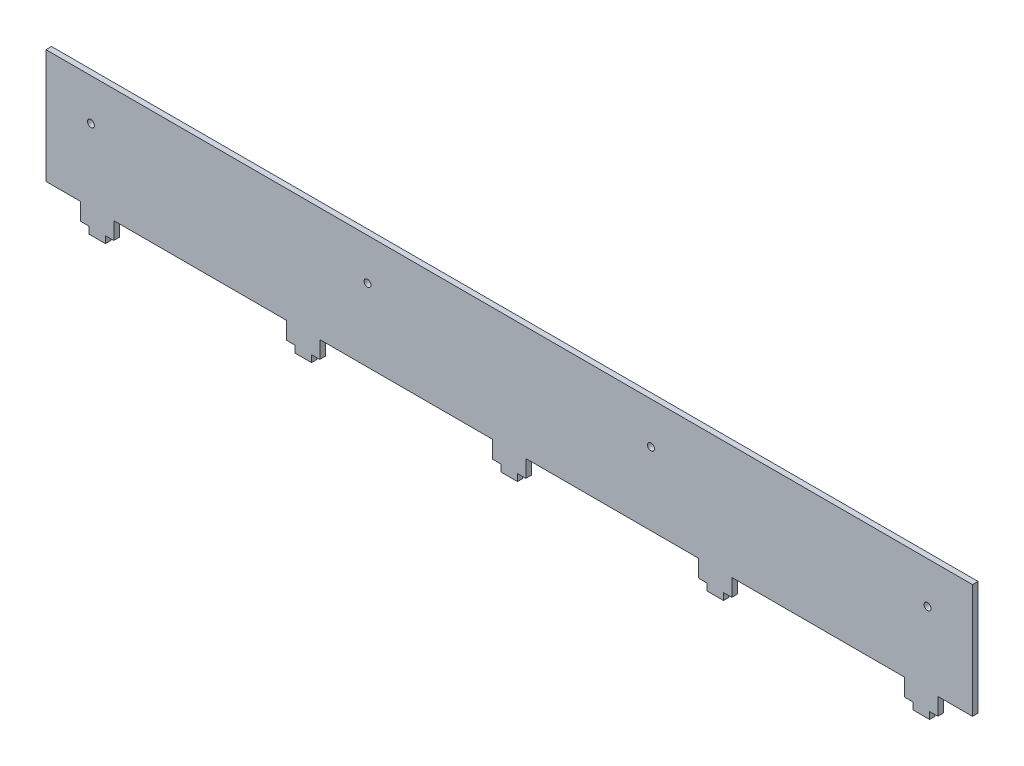
SolidWorks part; units mm, degrees
ref_plane "Спереди" through (0, 0, 0) normal (0, 0, 1) x (1, 0, 0)
ref_plane "Сверху" through (0, 0, 0) normal (0, 1, 0) x (1, 0, 0)
ref_plane "Справа" through (0, 0, 0) normal (1, 0, 0) x (0, 0, -1)
sketch "Эскиз1" plane through (0, 0, 0) normal (0, 0, 1) x (1, 0, 0)
  line L1 (-335, -47.5) -> (335, -47.5)
  line L2 (-335, -47.5) -> (-335, 47.5)
  line L3 (-335, 47.5) -> (335, 47.5)
  line L4 (335, -47.5) -> (335, 47.5)
  line L5 (0, 47.5) -> (0, -47.5) construction
  line L6 (-335, 0) -> (335, 0) construction
  point P0 (0, 0)
  dimension "D1" = 95
  dimension "D2" = 670
extrude "Бобышка-Вытянуть1" add sketch "Эскиз1" along normal mid plane 4
sketch "Эскиз2" plane through (0, 0, 2) normal (0, 0, 1) x (1, 0, 0)
  line L0 (-335, -47.5) -> (335, -47.5) construction
  line L9 (-435, -35.0456) -> (-310, -35.0456)
  line L10 (-435, -35.0456) -> (-435, -47.5)
  line L11 (-435, -47.5) -> (-310, -47.5)
  line L12 (-310, -35.0456) -> (-310, -47.5)
  line L14 (-286, -35.0456) -> (-161, -35.0456)
  line L15 (-286, -35.0456) -> (-286, -47.5)
  line L16 (-286, -47.5) -> (-161, -47.5)
  line L17 (-161, -35.0456) -> (-161, -47.5)
  line L18 (-137, -35.0456) -> (-12, -35.0456)
  line L19 (-137, -35.0456) -> (-137, -47.5)
  line L20 (-137, -47.5) -> (-12, -47.5)
  line L21 (-12, -35.0456) -> (-12, -47.5)
  line L22 (12, -35.0456) -> (137, -35.0456)
  line L23 (12, -35.0456) -> (12, -47.5)
  line L24 (12, -47.5) -> (137, -47.5)
  line L25 (137, -35.0456) -> (137, -47.5)
  line L26 (161, -35.0456) -> (286, -35.0456)
  line L27 (161, -35.0456) -> (161, -47.5)
  line L28 (161, -47.5) -> (286, -47.5)
  line L29 (286, -35.0456) -> (286, -47.5)
  line L30 (310, -35.0456) -> (435, -35.0456)
  line L31 (310, -35.0456) -> (310, -47.5)
  line L32 (310, -47.5) -> (435, -47.5)
  line L33 (435, -35.0456) -> (435, -47.5)
  point P25 (-137, -41.2728)
  point P26 (137, -41.2728)
  dimension "D6" = 125
  dimension "D3" = 125
  dimension "D4" = 125
  dimension "D9" = 125
  dimension "D11" = 125
  dimension "D5" = 24
  dimension "D2" = 24
  dimension "D7" = 24
  dimension "D8" = 24
  dimension "D10" = 24
  dimension "D12" = 125
  dimension "D13" = 12
extrude "Вырез-Вытянуть1" cut sketch "Эскиз2" against normal through all
sketch "Эскиз3" [suppressed] plane through (0, 0, 2) normal (0, 0, 1) x (1, 0, 0)
  line L0 (-328, 5.9544) -> (-328, -6.0456)
  line L1 (-328, -6.0456) -> (-318, -6.0456)
  line L2 (-318, -6.0456) -> (-318, -20.0456)
  line L3 (-318, -20.0456) -> (318, -20.0456)
  line L4 (318, -20.0456) -> (318, -6.0456)
  line L5 (318, -6.0456) -> (328, -6.0456)
  line L6 (328, -6.0456) -> (328, 5.9544)
  line L7 (328, 5.9544) -> (290, 5.9544)
  line L8 (290, 5.9544) -> (280, 35.5)
  line L9 (280, 35.5) -> (240, 35.5)
  line L10 (240, 35.5) -> (230, 5.9544)
  line L11 (230, 5.9544) -> (-230, 5.9544)
  line L12 (-230, 5.9544) -> (-240, 35.5)
  line L13 (-240, 35.5) -> (-280, 35.5)
  line L14 (-280, 35.5) -> (-290, 5.9544)
  line L15 (-290, 5.9544) -> (-328, 5.9544)
  line L16 (0, 0) -> (0, 91.1092) construction
  line L17 (-260, 35.5) -> (-260, 12.7826) construction
  line L18 (260, 35.5) -> (260, 0) construction
  line L19 (-12, -35.0456) -> (-137, -35.0456) construction
  line L20 (-335, 47.5) -> (-335, -35.0456) construction
  line L21 (335, 47.5) -> (-335, 47.5) construction
  dimension "D1" = 15
  dimension "D2" = 14
  dimension "D3" = 12
  dimension "D4" = 60
  dimension "D5" = 38
  dimension "D6" = 7
  dimension "D7" = 17
  dimension "D8" = 12
  dimension "D9" = 40
extrude "Вырез-Вытянуть2" [suppressed] cut sketch "Эскиз3" against normal through all
fillet "Скругление1" [suppressed] radius 10
fillet "Скругление6" [suppressed] radius 2
sketch "Эскиз4" [suppressed] plane through (0, 0, 2) normal (0, 0, 1) x (1, 0, 0)
  circle A1 centre (-302.5, -27.5) radius 2.5
  circle A2 centre (-302.5, -27.5) radius 2.5
  circle A3 centre (0, -27.5) radius 2.5
  circle A4 centre (0, -27.5) radius 2.5
  circle A5 centre (302.5, -27.5) radius 2.5
  circle A6 centre (302.5, -27.5) radius 2.5
  circle A7 centre (-102.5, 17.5) radius 2.5
  circle A8 centre (-102.5, 17.5) radius 2.5
  circle A9 centre (102.5, 17.5) radius 2.5
  circle A10 centre (102.5, 17.5) radius 2.5
  circle A11 centre (-302.5, 17.5) radius 2.5
  circle A12 centre (-302.5, 17.5) radius 2.5
  circle A13 centre (302.5, 17.5) radius 2.5
  circle A14 centre (302.5, 17.5) radius 2.5
  dimension "D1" = 0
  dimension "D2" = 0
  dimension "D3" = 0
  dimension "D4" = 0
  dimension "D5" = 0
  dimension "D6" = 0
  dimension "D7" = 0
extrude "Вырез-Вытянуть3" [suppressed] cut sketch "Эскиз4" against normal through all
sketch "Эскиз5" plane through (0, 0, 2) normal (0, 0, 1) x (1, 0, 0)
  circle A7 centre (-102.5, 17.5) radius 2.5
  circle A8 centre (-102.5, 17.5) radius 2.5
  circle A9 centre (102.5, 17.5) radius 2.5
  circle A10 centre (102.5, 17.5) radius 2.5
  circle A11 centre (-302.5, 17.5) radius 2.5
  circle A12 centre (-302.5, 17.5) radius 2.5
  circle A13 centre (302.5, 17.5) radius 2.5
  circle A14 centre (302.5, 17.5) radius 2.5
  dimension "D4" = 0
  dimension "D5" = 0
  dimension "D6" = 0
  dimension "D7" = 0
extrude "Вырез-Вытянуть4" cut sketch "Эскиз5" against normal through all
sketch "Эскиз6" plane through (0, -47.5, 0) normal (0, -1, 0) x (1, 0, 0)
  line L0 (286, -2) -> (310, -2) construction
  line L2 (310, 2) -> (286, 2) construction
  line L4 (161, 2) -> (137, 2) construction
  line L6 (137, -2) -> (161, -2) construction
  line L8 (-12, -2) -> (12, -2) construction
  line L10 (12, 2) -> (-12, 2) construction
  line L12 (-161, -2) -> (-137, -2) construction
  line L14 (-137, 2) -> (-161, 2) construction
  line L16 (-310, -2) -> (-286, -2) construction
  line L18 (-286, 2) -> (-310, 2) construction
  line L20 (292, -2) -> (304, -2)
  line L21 (304, -2) -> (304, 2)
  line L22 (304, 2) -> (292, 2)
  line L23 (292, 2) -> (292, -2)
  line L24 (155, 2) -> (143, 2)
  line L25 (143, 2) -> (143, -2)
  line L26 (143, -2) -> (155, -2)
  line L27 (155, -2) -> (155, 2)
  line L28 (-6, -2) -> (6, -2)
  line L29 (6, -2) -> (6, 2)
  line L30 (6, 2) -> (-6, 2)
  line L31 (-6, 2) -> (-6, -2)
  line L32 (-155, -2) -> (-143, -2)
  line L33 (-143, -2) -> (-143, 2)
  line L34 (-143, 2) -> (-155, 2)
  line L35 (-155, 2) -> (-155, -2)
  line L36 (-304, -2) -> (-292, -2)
  line L37 (-292, -2) -> (-292, 2)
  line L38 (-292, 2) -> (-304, 2)
  line L39 (-304, 2) -> (-304, -2)
  line L40 (298, 2) -> (298, -2) construction
  line L41 (286, 2) -> (310, 2) construction
  line L42 (149, 2) -> (149, -2) construction
  line L43 (137, 2) -> (161, 2) construction
  line L44 (0, 2) -> (0, -2) construction
  line L45 (-12, 2) -> (12, 2) construction
  line L46 (-149, 2) -> (-149, -2) construction
  line L47 (-161, 2) -> (-137, 2) construction
  line L48 (-298, 2) -> (-298, -2) construction
  line L49 (-310, 2) -> (-286, 2) construction
  point P18 (0, 0)
  point P20 (0, 0)
  point P62 (-292, 0)
  dimension "D1" = 12
  dimension "D2" = 12
  dimension "D3" = 12
  dimension "D4" = 12
  dimension "D5" = 12
extrude "Бобышка-Вытянуть2" add sketch "Эскиз6" along normal blind 5
equation "\"D3@Эскиз2\"=\"D6@Эскиз2\""
equation "\"D4@Эскиз2\"=\"D6@Эскиз2\""
equation "\"D9@Эскиз2\"=\"D6@Эскиз2\""
equation "\"D2@Эскиз2\"=\"D5@Эскиз2\""
equation "\"D7@Эскиз2\"=\"D5@Эскиз2\""
equation "\"D10@Эскиз2\"=\"D5@Эскиз2\""
equation "\"D12@Эскиз2\"=\"D6@Эскиз2\""
equation "\"D13@Эскиз2\"=\"D5@Эскиз2\"/2"
